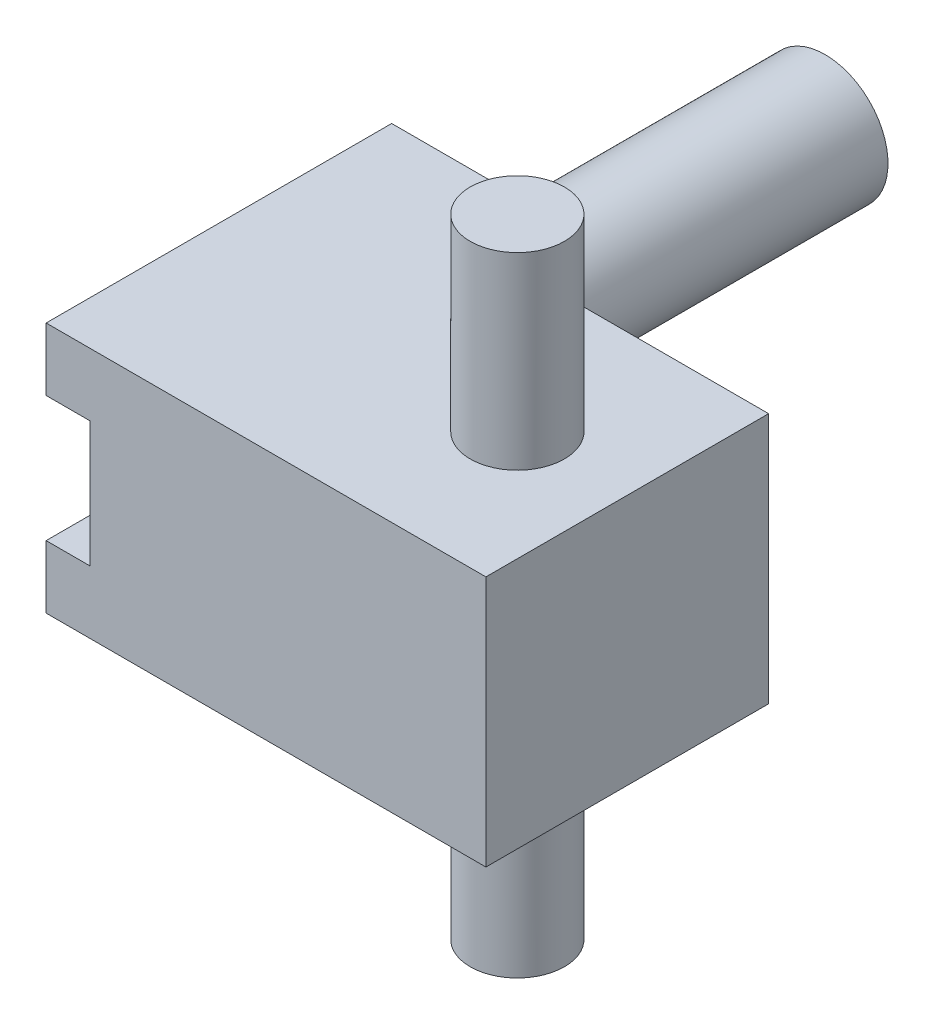
SolidWorks part; units mm, degrees
ref_plane "Alzado" through (0, 0, 0) normal (0, 0, 1) x (1, 0, 0)
ref_plane "Planta" through (0, 0, 0) normal (0, 1, 0) x (1, 0, 0)
ref_plane "Vista lateral" through (0, 0, 0) normal (1, 0, 0) x (0, 0, -1)
sketch "Croquis2" plane through (0, 0, 0) normal (0, 0, 1) x (1, 0, 0)
  line L0 (0, 0) -> (0, 40)
  line L1 (0, 40) -> (70, 40)
  line L2 (70, 40) -> (70, 0)
  line L3 (70, 0) -> (0, 0)
  dimension "D1" = 40
  dimension "D2" = 70
extrude "Saliente-Extruir1" add sketch "Croquis2" along normal blind 45
sketch "Croquis3" plane through (0, 0, 0) normal (0, 0, -1) x (-1, 0, 0)
  line L0 (0, 0) -> (0, 10)
  line L1 (0, 40) -> (0, 0) construction
  line L2 (0, 10) -> (0, 30)
  line L3 (0, 30) -> (0, 40)
  line L4 (0, 10) -> (-70, 10)
  line L5 (-70, 0) -> (-70, 40) construction
  line L6 (-70, 10) -> (-70, 30)
  line L8 (0, 30) -> (-7, 30)
  line L9 (-7, 30) -> (-7, 10)
  line L10 (-7, 10) -> (-47.5, 10)
  line L11 (-7, 10) -> (-7, 30)
  line L12 (-7, 30) -> (-47.5, 30)
  line L13 (-47.5, 10) -> (-47.5, 30)
  dimension "D1" = 10
  dimension "D2" = 10
  dimension "D3" = 7
  dimension "D4" = 40.5
extrude "Cortar-Extruir1" cut sketch "Croquis3" against normal blind 39 contours L13 L4 L9 L12 region at (27.25, 20, 0)
sketch "Croquis4" plane through (0, 0, 0) normal (0, 0, -1) x (-1, 0, 0)
  line L0 (-7, 10) -> (0, 10)
  line L1 (0, 40) -> (0, 0) construction
  line L2 (0, 10) -> (0, 30)
  line L3 (0, 30) -> (-7, 30)
  line L4 (-7, 30) -> (-7, 10)
  line L6 (-47.5, 10) -> (-54.5, 10)
  line L7 (-47.5, 10) -> (-47.5, 30)
  line L8 (-47.5, 30) -> (-54.5, 30)
  line L9 (-54.5, 10) -> (-54.5, 30)
  dimension "D1" = 7
extrude "Cortar-Extruir2" cut sketch "Croquis4" against normal blind 12 contours L4 L0 L2 L3 | L7 L6 L9 L8
sketch "Croquis5" plane through (0, 0, 0) normal (-1, 0, 0) x (0, 0, 1)
  line L0 (25, 10) -> (25, 30)
  line L1 (25, 10) -> (45, 10)
  line L2 (45, 40) -> (45, 0) construction
  line L3 (45, 10) -> (45, 30)
  line L4 (45, 30) -> (25, 30)
  dimension "D1" = 20
extrude "Cortar-Extruir4" cut sketch "Croquis5" against normal blind 7
sketch "Croquis6" plane through (0, 40, 0) normal (0, 1, 0) x (1, 0, 0)
  line L0 (70, 0) -> (0, 0) construction
  line L1 (70, -45) -> (35, -45) construction
  line L2 (70, -45) -> (70, 0) construction
  line L3 (70, 0) -> (35, 0) construction
  line L4 (35, -45) -> (35, 0) construction
  line L5 (35, 0) -> (70, -45) construction
  circle A0 centre (52.5, -22.5) radius 7.5
  dimension "D1" = 15
  dimension "D2" = 35
extrude "Saliente-Extruir3" add sketch "Croquis6" along normal blind 30
sketch "Croquis8" plane through (0, 0, 0) normal (0, -1, 0) x (1, 0, 0)
  line L0 (0, 0) -> (70, 0) construction
  line L1 (70, 45) -> (35, 45) construction
  line L2 (70, 45) -> (70, 0) construction
  line L3 (70, 0) -> (35, 0) construction
  line L4 (35, 45) -> (35, 0) construction
  line L5 (70, 45) -> (35, 0) construction
  circle A0 centre (52.5, 22.5) radius 7.5
  dimension "D2" = 15
  dimension "D1" = 35
extrude "Saliente-Extruir4" add sketch "Croquis8" along normal blind 30
sketch "Croquis9" plane through (0, 0, 0) normal (0, 0, -1) x (-1, 0, 0)
  line L0 (0, 40) -> (-30, 40)
  line L1 (-70, 40) -> (0, 40) construction
  line L2 (-30, 40) -> (-30, 0)
  line L3 (0, 0) -> (-70, 0) construction
  line L4 (-30, 0) -> (0, 0)
  line L5 (0, 0) -> (0, 40)
  dimension "D1" = 30
extrude "Saliente-Extruir5" add sketch "Croquis9" along normal blind 10
sketch "Croquis10" plane through (0, 0, -10) normal (0, 0, -1) x (-1, 0, 0)
  line L0 (-30, 0) -> (0, 40) construction
  circle A0 centre (-15, 20) radius 10
  dimension "D1" = 20
extrude "Saliente-Extruir6" add sketch "Croquis10" along normal blind 54
